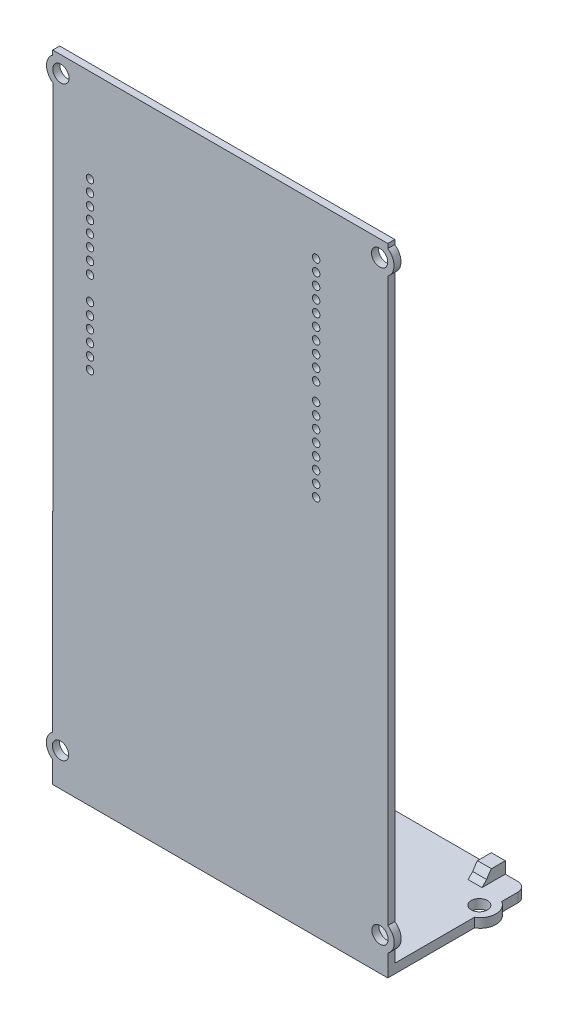
SolidWorks part; units mm, degrees
ref_plane "Front Plane" through (0, 0, 0) normal (0, 0, 1) x (1, 0, 0)
ref_plane "Top Plane" through (0, 0, 0) normal (0, 1, 0) x (1, 0, 0)
ref_plane "Right Plane" through (0, 0, 0) normal (1, 0, 0) x (0, 0, -1)
sketch "Sketch1" plane through (0, 0, 0) normal (0, 0, 1) x (1, 0, 0)
  line L0 (-31.5, -134.5) -> (31.5, -134.5)
  line L28 (-35.994, -6.0543) -> (-36, -126.951)
  line L29 (-36, -132.049) -> (-36, -134.5)
  line L30 (-36, -134.5) -> (-31.5, -134.5)
  line L31 (-31.5, -134.5) -> (-31.5, -132.049) construction
  line L32 (-31.5, -126.951) -> (-31.5, -7) construction
  line L33 (-31.5, -7) -> (31.5, -7) construction
  line L34 (31.5, -7) -> (31.5, -126.951) construction
  line L35 (31.5, -132.049) -> (31.5, -134.5) construction
  line L36 (31.5, -134.5) -> (36, -134.5)
  line L37 (36, -134.5) -> (36, -132.049)
  line L38 (36, -126.951) -> (36, -6.049)
  line L39 (36, -0.951) -> (36, 0)
  line L40 (36, 0) -> (-36, 0)
  line L41 (-36, 0) -> (-36, -0.951)
  circle A0 centre (-34.3286, -129.5) radius 1.75
  circle A1 centre (34.3232, -129.5) radius 1.75
  circle A2 centre (34.2427, -3.5) radius 1.75
  circle A3 centre (-34.2441, -3.5006) radius 1.75
  arc A12 (-36, -126.951) -> (-36, -132.049) centre (-34.3286, -129.5) ccw
  arc A13 (-31.5, -132.049) -> (-31.5, -126.951) centre (-34.3286, -129.5) ccw construction
  arc A14 (31.5, -126.951) -> (31.5, -132.049) centre (34.3232, -129.5) ccw construction
  arc A15 (36, -132.049) -> (36, -126.951) centre (34.3232, -129.5) ccw
  arc A16 (36, -6.049) -> (36, -0.951) centre (34.2427, -3.5) ccw
  arc A17 (-36, -0.951) -> (-35.994, -6.0543) centre (-34.2441, -3.5006) ccw
  dimension "D2" = 3.5
extrude "Boss-Extrude1" add sketch "Sketch1" along normal blind 1.5
sketch "Sketch2" plane through (-36, 0, 0) normal (-1, 0, 0) x (0, 0, 1)
  line L0 (1.5, -134.5) -> (1.5, -136.7)
  line L1 (1.5, -136.7) -> (-40, -136.7)
  line L2 (-40, -136.7) -> (-40, -134.7)
  line L3 (-40, -134.7) -> (0, -134.7)
  line L4 (0, -134.7) -> (0, -134.5)
  line L10 (0, -132.049) -> (0, -134.5)
  line L11 (0, -134.5) -> (1.5, -134.5)
  line L12 (1.5, -134.5) -> (1.5, -132.049)
  line L13 (1.5, -132.049) -> (0, -132.049)
  line L14 (0, -132.049) -> (0, -134.5)
  line L16 (1.5, -134.5) -> (1.5, -132.049)
  line L17 (1.5, -132.049) -> (0, -132.049)
  dimension "D1" = 2
  dimension "D2" = 0.2
  dimension "D4" = 40
  dimension "D3" = 0
extrude "Boss-Extrude2" add sketch "Sketch2" against normal up to surface (72 mm away) up to face at (36, -133.2745, 0.75)
sketch "Sketch3" plane through (0, 0, 0) normal (1, 0, 0) x (0, 0, -1)
  line L0 (0, -119.7) -> (15, -134.7)
  line L1 (0, -126.951) -> (0, -6.049) construction
  line L2 (40, -134.7) -> (0, -134.7) construction
  line L3 (15, -134.7) -> (0, -134.7)
  line L4 (0, -134.7) -> (0, -119.7)
  dimension "D1" = 15
extrude "Boss-Extrude3" add sketch "Sketch3" along normal blind 1.5 and the other way blind 1.5
sketch "Sketch4" plane through (0, -136.7, 0) normal (0, -1, 0) x (1, 0, 0)
  line L0 (-36, -17.1528) -> (-36, -22.963)
  line L1 (36, -17.1528) -> (36, -22.963)
  line L2 (-36, -40) -> (-36, 1.5) construction
  line L4 (36, 1.5) -> (36, -40) construction
  arc A2 (-36, -17.1528) -> (-36, -22.963) centre (-34.2684, -20.0579) ccw
  arc A3 (36, -22.963) -> (36, -17.1528) centre (34.3298, -20.0579) ccw
extrude "Boss-Extrude4" add sketch "Sketch4" against normal blind 2
sketch "Sketch5" plane through (0, -136.7, 0) normal (0, -1, 0) x (1, 0, 0)
  line L0 (-37.6504, -20.0579) -> (-36.0004, -20.0579) construction
  line L1 (36.0308, -20.0579) -> (37.6808, -20.0579) construction
  circle A0 centre (-34.2539, -19.9468) radius 1.75
  circle A1 centre (34.289, -19.8892) radius 1.75
  arc A2 (-36, -17.1528) -> (-36, -22.963) centre (-34.2684, -20.0579) ccw construction
  arc A3 (36, -22.963) -> (36, -17.1528) centre (34.3298, -20.0579) ccw construction
  point P6 (-37.6504, -20.0579)
  point P7 (-36.0004, -20.0579)
  dimension "D1" = 3.5
  dimension "D2" = 1.65
extrude "Cut-Extrude1" cut sketch "Sketch5" against normal blind 2
sketch "Sketch6" plane through (0, -136.7, 0) normal (0, -1, 0) x (1, 0, 0)
  line L0 (-36.784, -28.4468) -> (36, -28.4468)
  point P0 (-34.2539, -19.9468)
  dimension "D1" = 8.5
extrude "Cut-Extrude2" cut sketch "Sketch6" against normal through all and the other way through all
sketch "Sketch7" plane through (0, -136.7, 0) normal (0, -1, 0) x (1, 0, 0)
  line L0 (-36, -28.4468) -> (36, -28.4468) construction
  line L1 (-31.3, -28.4468) -> (-28.3, -28.4468)
  line L2 (-31.3, -28.4468) -> (-31.3, -24.4468)
  line L3 (-31.3, -24.4468) -> (-28.3, -24.4468)
  line L4 (-28.3, -28.4468) -> (-28.3, -24.4468)
  line L5 (-36, -25.7049) -> (-31.3, -25.7049) construction
  line L6 (31.3, -28.4468) -> (28.3, -28.4468)
  line L7 (31.3, -28.4468) -> (31.3, -24.4468)
  line L8 (31.3, -24.4468) -> (28.3, -24.4468)
  line L9 (28.3, -28.4468) -> (28.3, -24.4468)
  line L10 (-36, -28.4468) -> (-36, -22.963) construction
  line L11 (31.3, -24.4468) -> (36, -24.4468) construction
  line L12 (36, -22.963) -> (36, -28.4468) construction
  dimension "D1" = 4.7
  dimension "D2" = 3
  dimension "D3" = 4
extrude "Boss-Extrude6" add sketch "Sketch7" against normal blind 2.5 from surface at -2 starting at face at (34.289, -134.7, -21.6392)
fillet "Fillet1" radius 2 2 edges at (-36, -135.7, -28.4468) (36, -135.7, -28.4468)
chamfer "Chamfer1" distance 1 angle 45 4 edges at (-29.8, -132.2, -24.4468) (29.8, -132.2, -24.4468) (-29.8, -134.7, -24.4468) (29.8, -134.7, -24.4468)
fillet "Fillet2" radius 8 2 edges at (-29.8, -133.2, -24.4468) (29.8, -133.2, -24.4468)
sketch "Sketch8" plane through (0, -136.7, 0) normal (0, -1, 0) x (1, 0, 0)
  line L0 (-36, -17.1528) -> (-36, 1.5) construction
  line L1 (-31, -5.5) -> (4, -5.5)
  line L2 (-31, -5.5) -> (-31, -25.4468)
  line L3 (-31, -25.4468) -> (4, -25.4468)
  line L4 (4, -5.5) -> (4, -25.4468)
  line L5 (36, 1.5) -> (-36, 1.5) construction
  line L6 (-34, -28.4468) -> (34, -28.4468) construction
  dimension "D1" = 5
  dimension "D2" = 40
  dimension "D3" = 7
  dimension "D4" = 3
extrude "Cut-Extrude3" cut sketch "Sketch8" against normal blind 22.4262
sketch "Sketch10" plane through (0, 0, 1.5) normal (0, 0, 1) x (1, 0, 0)
  line L0 (36, 0) -> (-36, 0) construction
  line L2 (-35.994, -6.0543) -> (-36, -126.951) construction
  circle A0 centre (-27.9947, -20) radius 0.8
  circle A1 centre (-27.9947, -22.54) radius 0.8
  circle A2 centre (-27.9947, -25.08) radius 0.8
  circle A3 centre (-27.9947, -27.62) radius 0.8
  circle A4 centre (-27.9947, -30.16) radius 0.8
  circle A5 centre (-27.9947, -32.7) radius 0.8
  circle A6 centre (-27.9947, -35.24) radius 0.8
  circle A7 centre (-27.9947, -37.78) radius 0.8
  circle A8 centre (20.6053, -10.5) radius 0.8
  circle A9 centre (-27.9947, -42.86) radius 0.8
  circle A10 centre (-27.9947, -45.4) radius 0.8
  circle A11 centre (-27.9947, -47.94) radius 0.8
  circle A12 centre (-27.9947, -50.48) radius 0.8
  circle A13 centre (-27.9947, -53.02) radius 0.8
  circle A14 centre (-27.9947, -55.56) radius 0.8
  circle A15 centre (-27.9947, -40.32) radius 0.8 [skipped]
  circle A16 centre (20.6053, -13.04) radius 0.8
  circle A17 centre (20.6053, -15.58) radius 0.8
  circle A18 centre (20.6053, -18.12) radius 0.8
  circle A19 centre (20.6053, -20.66) radius 0.8
  circle A20 centre (20.6053, -23.2) radius 0.8
  circle A21 centre (20.6053, -25.74) radius 0.8
  circle A22 centre (20.6053, -28.28) radius 0.8
  circle A23 centre (20.6053, -30.82) radius 0.8
  circle A24 centre (20.6053, -33.36) radius 0.8
  circle A25 centre (20.6053, -37.16) radius 0.8
  circle A26 centre (20.6053, -39.7) radius 0.8
  circle A27 centre (20.6053, -42.24) radius 0.8
  circle A28 centre (20.6053, -44.78) radius 0.8
  circle A29 centre (20.6053, -47.32) radius 0.8
  circle A30 centre (20.6053, -49.86) radius 0.8
  circle A31 centre (20.6053, -52.4) radius 0.8
  circle A32 centre (20.6053, -54.94) radius 0.8
  dimension "D1" = 15
  dimension "D4" = 48.6
  dimension "D7" = 3.8
  dimension "D2" = 20
  dimension "D3" = 8
  dimension "D5" = 9.5
  dimension "D6" = 10
  dimension "D8" = 8
extrude "Cut-Extrude4" cut sketch "Sketch10" against normal up to next (1.5 mm away)
